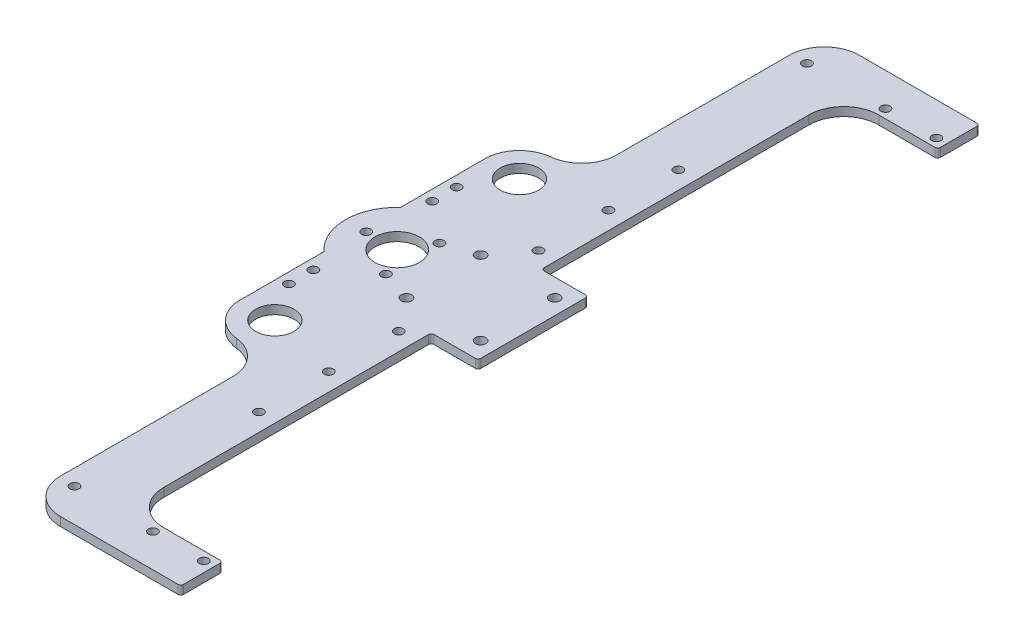
SolidWorks part; units mm, degrees
ref_plane "Front Plane" through (0, 0, 0) normal (0, 0, 1) x (1, 0, 0)
ref_plane "Top Plane" through (0, 0, 0) normal (0, 1, 0) x (1, 0, 0)
ref_plane "Right Plane" through (0, 0, 0) normal (1, 0, 0) x (0, 0, -1)
sketch "Sketch1" plane through (0, 0, 0) normal (0, 1, 0) x (1, 0, 0)
  line L0 (-67.9713, -52.7283) -> (-67.9713, -82.5864)
  line L6 (-67.9713, 4.9919) -> (-67.9713, -24.8662)
  line L17 (11.2115, 106.3552) -> (-32.5284, 106.3552)
  line L20 (-32.5284, -183.9497) -> (7.3984, -183.9497)
  line L24 (-10.2035, 91.1152) -> (11.2115, 91.1152)
  line L26 (7.3984, -183.9497) -> (11.2115, -183.9497)
  line L28 (-10.2035, -168.7097) -> (11.2115, -168.7097)
  line L30 (11.2115, -168.7097) -> (11.2115, -183.9497)
  line L31 (-45.2284, -108.5097) -> (-45.2284, -171.2497)
  line L32 (11.2115, 106.3552) -> (11.2115, 91.1152)
  line L33 (-45.2284, 93.6552) -> (-45.2284, 30.9152)
  line L34 (-22.9035, -156.0097) -> (-22.9035, -58.7973)
  line L35 (-22.9035, -38.7973) -> (-5.9035, -38.7973) construction
  line L40 (-5.9035, -38.7973) -> (-5.9035, -18.7973)
  line L41 (-5.9035, -38.7973) -> (-5.9035, -58.7973)
  line L42 (-5.9035, -18.7973) -> (-22.9035, -18.7973)
  line L43 (-5.9035, -58.7973) -> (-22.9035, -58.7973)
  line L44 (-22.9035, -18.7973) -> (-22.9035, 78.4152)
  arc A0 (-67.9713, -82.5864) -> (-56.6084, -95.8785) centre (-55.2885, -83.2473) ccw
  arc A1 (-45.2284, -108.5097) -> (-56.6084, -95.8785) centre (-57.9284, -108.5097) ccw
  arc A4 (-56.6084, 18.284) -> (-45.2284, 30.9152) centre (-57.9284, 30.9152) ccw
  arc A5 (-56.6084, 18.284) -> (-67.9713, 4.9919) centre (-55.2885, 5.6527) ccw
  arc A6 (-67.9713, -24.8662) -> (-67.9713, -52.7283) centre (-55.2885, -38.7973) ccw
  arc A22 (-45.2284, 93.6552) -> (-32.5284, 106.3552) centre (-32.5284, 93.6552) cw
  arc A23 (-45.2284, -171.2497) -> (-32.5284, -183.9497) centre (-32.5284, -171.2497) ccw
  arc A24 (-22.9035, 78.4152) -> (-10.2035, 91.1152) centre (-10.2035, 78.4152) cw
  arc A25 (-22.9035, -156.0097) -> (-10.2035, -168.7097) centre (-10.2035, -156.0097) ccw
  circle A30 centre (-55.2885, -83.2473) radius 6.985 construction
  circle A31 centre (-64.1613, -69.2773) radius 1.65 construction
  circle A32 centre (-64.1613, -60.3873) radius 1.65 construction
  circle A33 centre (-55.2885, -38.7973) radius 8.0645 construction
  circle A34 centre (-49.6688, -29.0636) radius 1.65 construction
  circle A35 centre (-49.6688, -48.531) radius 1.65 construction
  circle A36 centre (-66.528, -38.7973) radius 1.65 construction
  circle A37 centre (-64.1613, -17.2073) radius 1.65 construction
  circle A38 centre (-64.1613, -8.3173) radius 1.65 construction
  circle A39 centre (-55.2885, 5.6527) radius 6.985 construction
  circle A40 centre (-55.2885, -83.2473) radius 6.985
  circle A41 centre (-64.1613, -69.2773) radius 1.65
  circle A42 centre (-64.1613, -60.3873) radius 1.65
  circle A43 centre (-55.2885, -38.7973) radius 8.0645
  circle A44 centre (-49.6688, -29.0636) radius 1.65
  circle A45 centre (-49.6688, -48.531) radius 1.65
  circle A46 centre (-66.528, -38.7973) radius 1.65
  circle A47 centre (-64.1613, -17.2073) radius 1.65
  circle A48 centre (-64.1613, -8.3173) radius 1.65
  circle A49 centre (-55.2885, 5.6527) radius 6.985
  circle A50 centre (-29.342, 37.4027) radius 1.65 construction
  circle A51 centre (-29.342, 12.0027) radius 1.65 construction
  circle A52 centre (-29.342, -13.3973) radius 1.65 construction
  circle A54 centre (-29.342, -64.1973) radius 1.65 construction
  circle A55 centre (-29.342, -89.5973) radius 1.65 construction
  circle A56 centre (-29.342, -114.9973) radius 1.65 construction
  circle A57 centre (-29.342, 37.4027) radius 1.65
  circle A58 centre (-29.342, 12.0027) radius 1.65
  circle A59 centre (-29.342, -13.3973) radius 1.65
  circle A61 centre (-29.342, -64.1973) radius 1.65
  circle A62 centre (-29.342, -89.5973) radius 1.65
  circle A63 centre (-29.342, -114.9973) radius 1.65
  point P58 (-45.2284, 106.3552)
  dimension "D3" = 66.5
  dimension "D5" = 15.24
  dimension "D6" = 10.0601
  dimension "D7" = 32.385
  dimension "D8" = 62.74
  dimension "D44" = 12.7
  dimension "D46" = 12.7
  dimension "D47" = 12.7
  dimension "D1" = 17
  dimension "D2" = 20
extrude "Boss-Extrude1" add sketch "Sketch1" along normal blind 3.175 contours A25 A24 L24 L32 A22 A4 A5 L6 A6 L0 A0 A1 A23 L20 L26 L30 L28 A63 A62 A61 A59 A58 A57 A49 A48 A47 A46 region at (-34.5755, 0, 38.7973)
sketch "Sketch4" plane through (0, 3.175, 0) normal (0, 1, 0) x (1, 0, 0)
  circle A0 centre (7.529, 94.2902) radius 1.65
  circle A1 centre (-10.971, 94.2902) radius 1.65
  circle A2 centre (-39.471, 94.2902) radius 1.65
  circle A3 centre (-39.471, -171.8847) radius 1.65
  circle A4 centre (-10.971, -171.8847) radius 1.65
  circle A5 centre (7.529, -171.8847) radius 1.65
  dimension "D1" = 3.3
extrude "Cut-Extrude1" cut sketch "Sketch4" against normal through all
sketch "Sketch5" plane through (0, 3.175, 0) normal (0, 1, 0) x (1, 0, 0)
  circle A1 centre (-11.5006, -25.3269) radius 1.8986
  circle A2 centre (-38.4414, -25.3269) radius 1.8986
  circle A5 centre (-38.4414, -52.2677) radius 1.8986
  circle A6 centre (-11.5006, -52.2677) radius 1.8986
  point P9 (-38.4414, -52.2677)
  point P17 (-11.5006, -52.2677)
  point P18 (-11.5006, -25.3269)
  point P19 (-38.4414, -52.2677)
  dimension "D1" = 3.7973
extrude "Cut-Extrude2" cut sketch "Sketch5" against normal through all
fillet "Fillet1" radius 1 8 edges at (-22.9035, 1.5875, 18.7973) (-22.9035, 1.5875, 58.7973) (11.2115, 1.5875, 183.9497) (11.2115, 1.5875, 168.7097) (-5.9035, 1.5875, 58.7973) (-5.9035, 1.5875, 18.7973) (11.2115, 1.5875, -106.3552) (11.2115, 1.5875, -91.1152)
